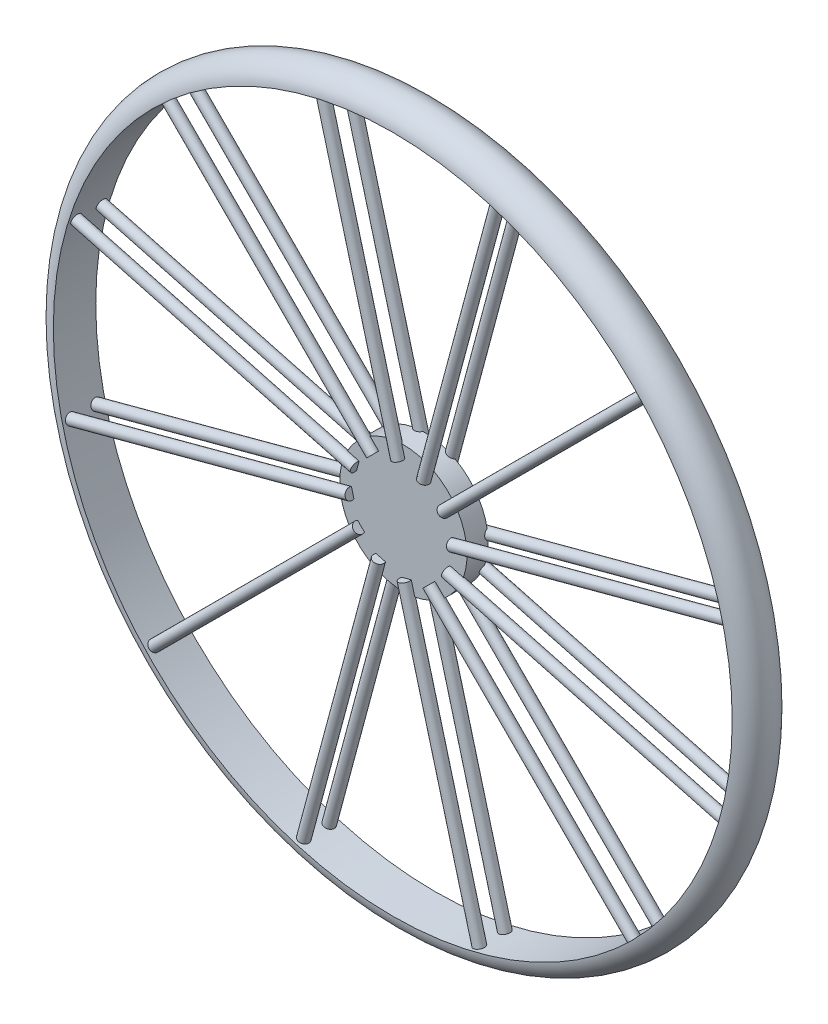
SolidWorks part; units mm, degrees
ref_plane "Front Plane" through (0, 0, 0) normal (0, 0, 1) x (1, 0, 0)
ref_plane "Top Plane" through (0, 0, 0) normal (0, 1, 0) x (1, 0, 0)
ref_plane "Right Plane" through (0, 0, 0) normal (1, 0, 0) x (0, 0, -1)
sketch "Sketch1" plane through (0, 0, 0) normal (0, 1, 0) x (1, 0, 0)
  line L0 (0, 0) -> (0, -25.4)
  line L1 (0, 0) -> (0, 25.4)
  arc A0 (0, -25.4) -> (0, 25.4) centre (1.8597, 0) cw
sketch "Sketch3" plane through (0, 0, 0) normal (0, 1, 0) x (1, 0, 0)
  line L0 (406.4, 0) -> (406.4, 47.6397)
  line L1 (0, 0) -> (0, -25.4) construction
  dimension "D1" = 406.4
revolve "Revolve1" add sketch "Sketch1" angle 360 about L0
sketch "Sketch4" plane through (0, 0, 0) normal (0, 0, 1) x (1, 0, 0)
  circle A0 centre (406.4, 0) radius 76.2
extrude "Boss-Extrude2" add sketch "Sketch4" along normal blind 12.7 separate body
sketch "Sketch6" plane through (0, 0, 0) normal (0, 0, -1) x (-1, 0, 0)
  circle A0 centre (-406.4, 0) radius 76.2
extrude "Boss-Extrude3" add sketch "Sketch6" along normal blind 12.7
ref_plane "Plane1" through (0, 0, 15.24) normal (0, 0, 1) x (1, 0, 0)
sketch "Sketch7" plane through (0, 0, 15.24) normal (0, 0, 1) x (1, 0, 0)
  line L0 (457.0554, 33.698) -> (702.891, 279.5336)
revolve "Revolve-Thin3" add sketch "Sketch7" angle 360 about L0 wall 6.35
ref_axis "Axis2" through (406.4, 0, 0) along (0, 0, -1)
pattern_circular "CirPattern2" count 12 every 30 about axis through (406.4, 0, 0) along (0, 0, -1) of "Revolve-Thin3"
mirror "Mirror1" about plane through (0, 0, 0) normal (0, 0, 1) of "CirPattern2"
